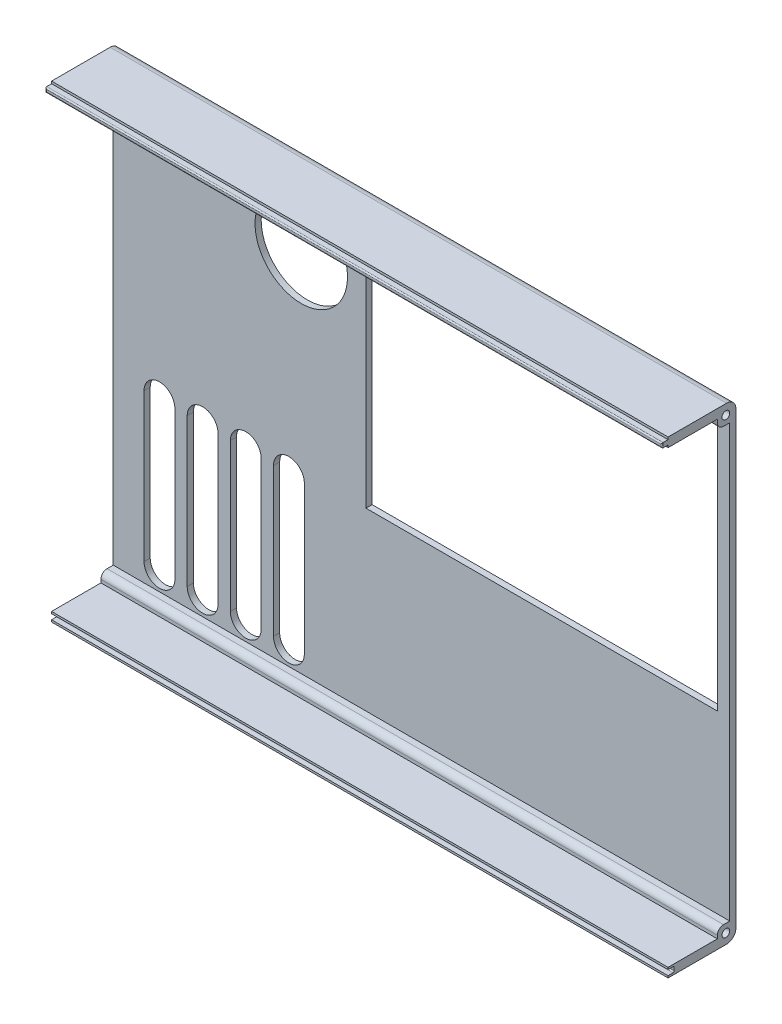
SolidWorks part; units mm, degrees
ref_plane "Front Plane" through (0, 0, 0) normal (0, 0, 1) x (1, 0, 0)
ref_plane "Top Plane" through (0, 0, 0) normal (0, 1, 0) x (1, 0, 0)
ref_plane "Right Plane" through (0, 0, 0) normal (1, 0, 0) x (0, 0, -1)
sketch "Sketch1" plane through (0, 0, 0) normal (0, 0, 1) x (1, 0, 0)
  line L1 (105, -90.3987) -> (-95, -90.3987)
  line L2 (105, -90.3987) -> (105, 61.6013)
  line L3 (105, 61.6013) -> (-95, 61.6013)
  line L4 (-95, -90.3987) -> (-95, 61.6013)
  line L5 (105, -90.3987) -> (-95, 61.6013) construction
  line L6 (105, 61.6013) -> (-95, -90.3987) construction
  point P0 (5, -14.3987)
  dimension "D1" = 200
  dimension "D2" = 152
extrude "body" add sketch "Sketch1" along normal blind 2
sketch "Sketch3" plane through (0, 0, 0) normal (0, 0, -1) x (-1, 0, 0)
  line L0 (95, -54.3987) -> (-105, -54.3987) construction
  line L1 (95, 61.6013) -> (95, -90.3987) construction
  line L2 (-105, -90.3987) -> (-105, 61.6013) construction
  line L3 (66, -78.3987) -> (66, -30.3987) construction
  line L4 (61, -78.3987) -> (61, -30.3987)
  line L5 (71, -78.3987) -> (71, -30.3987)
  line L6 (95, -30.3987) -> (-105, -30.3987) construction
  line L7 (80, -78.3987) -> (80, -30.3987) construction
  line L8 (95, -78.3987) -> (-105, -78.3987) construction
  line L9 (75, -78.3987) -> (75, -30.3987)
  line L10 (85, -78.3987) -> (85, -30.3987)
  line L11 (52, -78.3987) -> (52, -30.3987) construction
  line L12 (47, -78.3987) -> (47, -30.3987)
  line L13 (57, -78.3987) -> (57, -30.3987)
  line L14 (38, -78.3987) -> (38, -30.3987) construction
  line L15 (33, -78.3987) -> (33, -30.3987)
  line L16 (43, -78.3987) -> (43, -30.3987)
  line L17 (95, -90.3987) -> (95, 61.6013) construction
  line L18 (-105, 61.6013) -> (95, 61.6013) construction
  line L19 (95, -90.3987) -> (-105, -90.3987) construction
  line L20 (-105, -90.3987) -> (-105, 61.6013) construction
  circle A0 centre (34, 34.6013) radius 15
  arc A1 (61, -78.3987) -> (71, -78.3987) centre (66, -78.3987) ccw
  arc A2 (71, -30.3987) -> (61, -30.3987) centre (66, -30.3987) ccw
  arc A3 (75, -78.3987) -> (85, -78.3987) centre (80, -78.3987) ccw
  arc A4 (85, -30.3987) -> (75, -30.3987) centre (80, -30.3987) ccw
  arc A5 (47, -78.3987) -> (57, -78.3987) centre (52, -78.3987) ccw
  arc A6 (57, -30.3987) -> (47, -30.3987) centre (52, -30.3987) ccw
  arc A7 (33, -78.3987) -> (43, -78.3987) centre (38, -78.3987) ccw
  arc A8 (43, -30.3987) -> (33, -30.3987) centre (38, -30.3987) ccw
  point P10 (66, -54.3987)
  point P21 (80, -54.3987)
  point P27 (52, -54.3987)
  point P34 (38, -54.3987)
  dimension "D1" = 30
  dimension "D2" = 27
  dimension "D3" = 61
  dimension "D4" = 10
  dimension "D5" = 12
  dimension "D6" = 24
  dimension "D7" = 4
  dimension "D8" = 10
  dimension "D9" = 10
  dimension "D10" = 10
  dimension "D11" = 10
  dimension "D12" = 4
  dimension "D13" = 52
  dimension "D14" = 4
extrude "fan_exhaust_grill" cut sketch "Sketch3" against normal through all
sketch "Sketch12" plane through (0, 0, 2) normal (0, 0, 1) x (1, 0, 0)
  line L0 (-95, -90.3987) -> (-95, 61.6013) construction
  line L1 (105, -90.3987) -> (-95, -90.3987)
  line L2 (105, -90.3987) -> (105, -84.3987)
  line L3 (105, -84.3987) -> (-95, -84.3987)
  line L4 (-95, -90.3987) -> (-95, -84.3987)
  line L6 (105, 61.6013) -> (-95, 61.6013)
  line L7 (105, 61.6013) -> (105, 55.6013)
  line L8 (105, 55.6013) -> (-95, 55.6013)
  line L9 (-95, 61.6013) -> (-95, 55.6013)
  dimension "D1" = 6
  dimension "D2" = 6
extrude "side_walls" add sketch "Sketch12" along normal blind 20
sketch "Sketch14" plane through (105, 0, 0) normal (1, 0, 0) x (0, 0, -1)
  line L0 (-22, -90.3987) -> (0, -90.3987) construction
  line L1 (0, -90.3987) -> (0, 61.6013) construction
  line L2 (-22, 61.6013) -> (0, 61.6013) construction
  circle A0 centre (-3.25, -87.1487) radius 1.25
  circle A1 centre (-3.25, 58.3513) radius 1.25
  dimension "D1" = 2.5
  dimension "D2" = 2.5
  dimension "D3" = 3.25
  dimension "D4" = 3.25
  dimension "D5" = 3.25
  dimension "D6" = 3.25
  dimension "D7" = 145.5
extrude "mount_holes_l" cut sketch "Sketch14" against normal blind 10 and the other way through all
sketch "Sketch16" plane through (-95, 0, 0) normal (-1, 0, 0) x (0, 0, 1)
  line L0 (0, -90.3987) -> (0, 61.6013) construction
  line L2 (22, 61.6013) -> (0, 61.6013) construction
  line L3 (22, -90.3987) -> (0, -90.3987) construction
  circle A0 centre (3.25, -87.1487) radius 1.25
  circle A1 centre (3.25, 58.3513) radius 1.25
  dimension "D1" = 2.5
  dimension "D4" = 2.5
  dimension "D2" = 3.25
  dimension "D3" = 3.25
  dimension "D5" = 3.25
  dimension "D6" = 3.25
extrude "mount_holes_r" cut sketch "Sketch16" against normal blind 10
sketch "Sketch18" plane through (105, 0, 0) normal (1, 0, 0) x (0, 0, -1)
  line L1 (-22, -84.3987) -> (-6, -84.3987)
  line L2 (-22, -84.3987) -> (-22, -87.3987)
  line L3 (-22, -87.3987) -> (-6, -87.3987)
  line L4 (-6, -84.3987) -> (-6, -87.3987)
  line L5 (-22, 55.6013) -> (-6, 55.6013)
  line L6 (-22, 55.6013) -> (-22, 58.6013)
  line L7 (-22, 58.6013) -> (-6, 58.6013)
  line L8 (-6, 55.6013) -> (-6, 58.6013)
  dimension "D1" = 3
  dimension "D2" = 16
  dimension "D3" = 3
  dimension "D4" = 16
extrude "wall_reduce" cut sketch "Sketch18" against normal through all
sketch "Sketch19" plane through (0, 0, 22) normal (0, 0, 1) x (1, 0, 0)
  line L0 (-95, -90.3987) -> (-95, 61.6013) construction
  line L1 (-95, -89.7487) -> (105, -89.7487)
  line L2 (-95, -89.7487) -> (-95, -88.0487)
  line L3 (-95, -88.0487) -> (105, -88.0487)
  line L4 (105, -89.7487) -> (105, -88.0487)
  line L5 (105, -90.3987) -> (105, 61.6013) construction
  line L6 (-95, -90.3987) -> (105, -90.3987) construction
  line L7 (-95, -87.3987) -> (105, -87.3987) construction
  dimension "D1" = 0.65
  dimension "D2" = 1.7
  dimension "D3" = 0.65
extrude "groove" cut sketch "Sketch19" against normal blind 2
sketch "Sketch20" plane through (0, 0, 22) normal (0, 0, 1) x (1, 0, 0)
  line L0 (-95, -90.3987) -> (-95, 61.6013) construction
  line L1 (-95, 59.3513) -> (105, 59.3513)
  line L2 (-95, 59.3513) -> (-95, 60.8513)
  line L3 (-95, 60.8513) -> (105, 60.8513)
  line L4 (105, 59.3513) -> (105, 60.8513)
  line L5 (105, -90.3987) -> (105, 61.6013) construction
  line L6 (105, 61.6013) -> (-95, 61.6013) construction
  dimension "D1" = 0.75
  dimension "D2" = 1.5
extrude "notch" add sketch "Sketch20" along normal blind 2
sketch "Sketch21" plane through (0, 0, 2) normal (0, 0, 1) x (1, 0, 0)
  line L0 (105, -90.3987) -> (105, 61.6013) construction
  line L1 (101, -27.3987) -> (-13, -27.3987)
  line L2 (101, -27.3987) -> (101, 54.6013)
  line L3 (101, 54.6013) -> (-13, 54.6013)
  line L4 (-13, -27.3987) -> (-13, 54.6013)
  line L5 (105, 61.6013) -> (-95, 61.6013) construction
  dimension "D1" = 114
  dimension "D2" = 82
  dimension "D3" = 4
  dimension "D4" = 7
extrude "batt_cut" cut sketch "Sketch21" against normal through all
fillet "Fillet1" radius 3 2 edges at (5, -90.3987, 0) (5, 61.6013, 0)
fillet "Fillet2" radius 2 2 edges at (5, -84.3987, 6) (5, 55.6013, 6)
fillet "Fillet3" radius 0.4 6 edges at (5, 60.8513, 24) (105, 60.1013, 24) (5, 59.3513, 24) (-95, 60.1013, 24) (5, -89.7487, 20) (5, -88.0487, 20)
